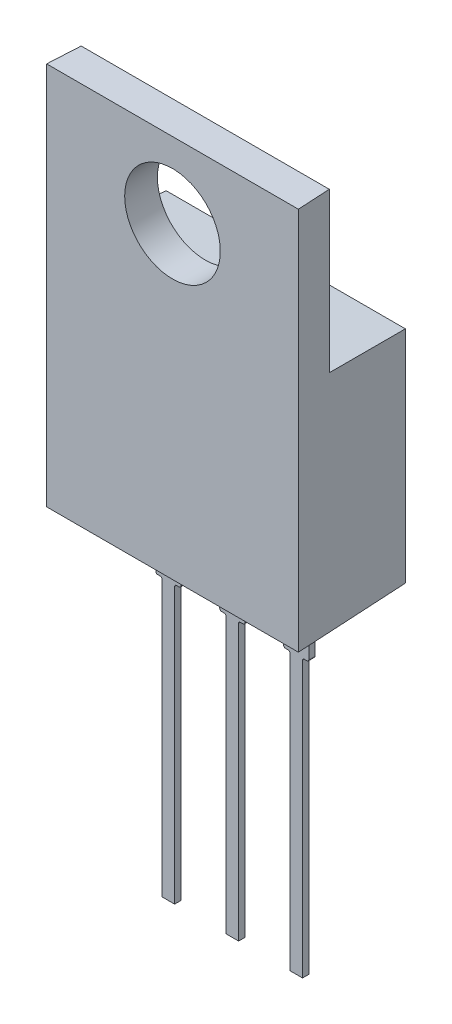
SolidWorks part; units mm, degrees
ref_plane "Front Plane" through (0, 0, 0) normal (0, 0, 1) x (1, 0, 0)
ref_plane "Top Plane" through (0, 0, 0) normal (0, 1, 0) x (1, 0, 0)
ref_plane "Right Plane" through (0, 0, 0) normal (1, 0, 0) x (0, 0, -1)
sketch "Sketch1" plane through (0, 0, 0) normal (0, 0, 1) x (1, 0, 0)
  line L1 (-5, 4.5) -> (5, 4.5)
  line L2 (-5, 4.5) -> (-5, -4.5)
  line L3 (-5, -4.5) -> (5, -4.5)
  line L4 (5, 4.5) -> (5, -4.5)
  line L5 (-5, 4.5) -> (5, -4.5) construction
  line L6 (-5, -4.5) -> (5, 4.5) construction
  point P0 (0, 0)
  dimension "D1" = 10
  dimension "D2" = 9
extrude "Boss-Extrude1" add sketch "Sketch1" along normal blind 4.5
chamfer "Chamfer1" distance 0.25 distance2 4.5 3 edges at (5, 0, 0) (0, 4.5, 0) (-5, 0, 0) first distance on face at (0, 0, 0)
sketch "Sketch3" plane through (0, -4.5, 0) normal (0, -1, 0) x (1, 0, 0)
  line L0 (4.9278, 3.2) -> (-4.9278, 3.2)
  line L1 (4.75, 0) -> (5, 4.5) construction
  line L2 (-5, 4.5) -> (-4.75, 0) construction
  line L3 (-5, 4.5) -> (5, 4.5) construction
  line L4 (-5, 4.5) -> (5, 4.5)
  line L5 (4.9278, 3.2) -> (5, 4.5)
  line L6 (-4.9278, 3.2) -> (-5, 4.5)
  line L7 (-5, 4.5) -> (-5.0101, 4.5124)
  line M2 (4.75, 0) -> (5, 4.5)
  line M3 (5, 4.5) -> (-5, 4.5)
  line M4 (-5, 4.5) -> (-4.75, 0)
  dimension "D1" = 1.3
extrude "Boss-Extrude3" add sketch "Sketch3" against normal blind 15.24 contours L0 M2 M3 M4 region at (0, -4.5, 3.8516)
sketch "Sketch4" plane through (0, 0, 3.2) normal (0, 0, -1) x (-1, 0, 0)
  line L0 (0, 0) -> (0, 10.74) construction
  line L1 (-4.9278, 10.74) -> (4.9278, 10.74) construction
  circle A0 centre (0, 7.74) radius 1.9
  dimension "D1" = 3.8
  dimension "D2" = 3
extrude "Cut-Extrude1" cut sketch "Sketch4" against normal through all
sketch "Sketch2" plane through (0, -4.5, 0) normal (0, -1, 0) x (1, 0, 0)
  line L0 (-4.8611, 2) -> (4.8611, 2) construction
  line L4 (-0.25, 1.875) -> (0.25, 1.875)
  line L5 (2.29, 2.125) -> (2.79, 2.125)
  line L6 (2.29, 2.125) -> (2.29, 1.875)
  line L7 (2.29, 1.875) -> (2.79, 1.875)
  line L8 (2.79, 2.125) -> (2.79, 1.875)
  line L9 (2.29, 2.125) -> (2.79, 1.875) construction
  line L10 (2.29, 1.875) -> (2.79, 2.125) construction
  line L11 (0.25, 2.125) -> (0.25, 1.875)
  line L12 (-0.25, 2.125) -> (0.25, 2.125)
  line L13 (-0.25, 2.125) -> (-0.25, 1.875)
  line L14 (-0.25, 2.125) -> (0.25, 1.875) construction
  line L15 (-0.25, 1.875) -> (0.25, 2.125) construction
  line L16 (-2.79, 1.875) -> (-2.29, 1.875)
  line L17 (-2.29, 2.125) -> (-2.29, 1.875)
  line L18 (-2.79, 2.125) -> (-2.29, 2.125)
  line L19 (-2.79, 2.125) -> (-2.79, 1.875)
  line L20 (-2.79, 2.125) -> (-2.29, 1.875) construction
  line L21 (-2.79, 1.875) -> (-2.29, 2.125) construction
  line L22 (-4.75, 0) -> (4.75, 0) construction
  line L23 (4.75, 0) -> (5, 4.5) construction
  line L25 (-5, 4.5) -> (-4.75, 0) construction
  line L28 (-5.33, 1.875) -> (-4.83, 1.875) [skipped]
  line L29 (-4.83, 2.125) -> (-4.83, 1.875) [skipped]
  line L30 (-5.33, 2.125) -> (-4.83, 2.125) [skipped]
  line L31 (-5.33, 2.125) -> (-5.33, 1.875) [skipped]
  line L32 (-5.33, 2.125) -> (-4.83, 1.875) construction
  line L33 (-5.33, 1.875) -> (-4.83, 2.125) construction
  point P8 (2.54, 2)
  point P13 (-5.08, 2)
  point P15 (0, 2)
  point P20 (-2.54, 2)
  dimension "D1" = 2
  dimension "D2" = 0.5
  dimension "D3" = 0.25
  dimension "D4" = 2.54
  dimension "D5" = 4
extrude "Boss-Extrude2" add sketch "Sketch2" along normal blind 13.5
sketch "Sketch5" plane through (0, -4.5, 0) normal (0, -1, 0) x (1, 0, 0)
  line L41 (3.04, 1.875) -> (3.04, 2.125)
  line L42 (3.04, 1.875) -> (3.04, 2.125)
  line L43 (3.04, 1.875) -> (2.04, 1.875)
  line L44 (2.04, 2.125) -> (2.04, 1.875)
  line L45 (2.04, 2.125) -> (2.04, 1.875)
  line L46 (2.04, 2.125) -> (3.04, 2.125)
  line L47 (0.5, 1.875) -> (-0.5, 1.875)
  line L48 (0.5, 1.875) -> (0.5, 2.125)
  line L49 (-0.5, 2.125) -> (0.5, 2.125)
  line L50 (-0.5, 2.125) -> (-0.5, 1.875)
  line L51 (-2.04, 1.875) -> (-3.04, 1.875)
  line L52 (-2.04, 1.875) -> (-2.04, 2.125)
  line L53 (-3.04, 2.125) -> (-2.04, 2.125)
  line L54 (-3.04, 2.125) -> (-3.04, 1.875)
  line L55 (3.04, 1.875) -> (0.5, 1.875) construction
  dimension "D4" = 2.54
  dimension "D1" = 0.25
  dimension "D2" = 0.25
  dimension "D3" = 3
extrude "Boss-Extrude4" add sketch "Sketch5" along normal blind 2.5
fillet "Fillet1" radius 0.075 12 edges at (-3.04, -7, 2) (-2.79, -7, 2) (-2.29, -7, 2) (-2.04, -7, 2) (-0.5, -7, 2) (-0.25, -7, 2) (0.25, -7, 2) (0.5, -7, 2) (2.04, -7, 2) (2.29, -7, 2) (2.79, -7, 2) (3.04, -7, 2)
